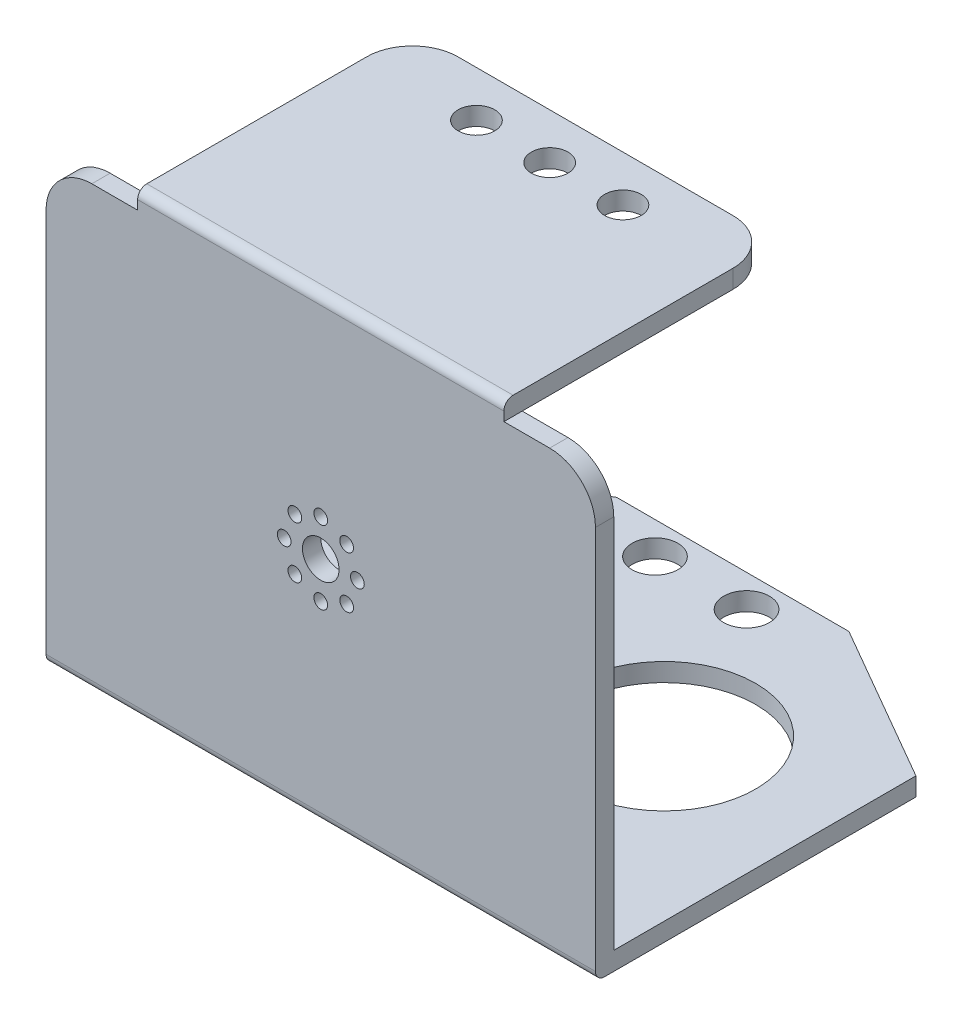
SolidWorks part; units mm, degrees
ref_plane "前视基准面" through (0, 0, 0) normal (0, 0, 1) x (1, 0, 0)
ref_plane "上视基准面" through (0, 0, 0) normal (0, 1, 0) x (1, 0, 0)
ref_plane "右视基准面" through (0, 0, 0) normal (1, 0, 0) x (0, 0, -1)
sketch "草图1" plane through (0, 0, 0) normal (0, 1, 0) x (1, 0, 0)
  line L0 (0, 0) -> (51111.788, 0) construction
  line L1 (0, 0) -> (0, 51111.788) construction
  line L2 (-12.6795, 0) -> (12.6795, 0)
  line L3 (12.6795, 0) -> (30, -10)
  line L4 (30, -10) -> (30, -45)
  line L5 (30, -45) -> (-30, -45)
  line L6 (-30, -45) -> (-30, -10)
  line L7 (-30, -10) -> (-12.6795, 0)
  dimension "D1" = 45
  dimension "D2" = 10
  dimension "D3" = 30
  dimension "D4" = 60
extrude "凸台-拉伸1" add sketch "草图1" along normal blind 2
sketch "草图2" plane through (0, 2, 0) normal (0, 1, 0) x (1, 0, 0)
  line L0 (30, -45) -> (30, -10) construction
  line L1 (-30, -45) -> (30, -45)
  line L2 (-30, -45) -> (-30, -43)
  line L3 (-30, -43) -> (30, -43)
  line L4 (30, -45) -> (30, -43)
  dimension "D1" = 2
extrude "凸台-拉伸2" add sketch "草图2" along normal blind 50 from surface starting at face at (0, 0, 18.3333)
fillet "圆角1" radius 1 1 edges at (0, 0, 45)
sketch "草图3" plane through (0, 0, 43) normal (0, 0, -1) x (-1, 0, 0)
  line L0 (0, 0) -> (0, 50000) construction
  line L1 (-20, 50) -> (20, 50)
  line L2 (-20, 50) -> (-20, 48)
  line L3 (-20, 48) -> (20, 48)
  line L4 (20, 50) -> (20, 48)
  line L5 (30, 50) -> (-30, 50) construction
  line L6 (30, 50) -> (30, 2) construction
  line L7 (-30, 50) -> (-20, 50)
  line L8 (-30, 50) -> (-30, 48)
  line L9 (-30, 48) -> (-20, 48)
  line L10 (-20, 50) -> (-20, 48)
  line L11 (20, 50) -> (30, 50)
  line L12 (20, 50) -> (20, 48)
  line L13 (20, 48) -> (30, 48)
  line L14 (30, 50) -> (30, 48)
  line M3 (30, 2) -> (30, 50)
  line M4 (30, 50) -> (-30, 50)
  line M5 (-30, 50) -> (-30, 2)
  dimension "D1" = 2
  dimension "D2" = 40
extrude "凸台-拉伸4" add sketch "草图3" along normal blind 30 from surface contours L3 L0 L1 L2 | L0 L3 L4 M4 region at (10, 49, 43) region at (-10, 49, 43) starting at face at (0, 25.5, 45)
extrude "切除-拉伸1" cut sketch "草图3<3>" against normal blind 30 contours L9 L2 M5 M4 | L4 L13 M3 M4 region at (25, 49, 43) region at (-25, 49, 43)
sketch "草图3<3>" plane through (0, 0, 43) normal (0, 0, -1) x (-1, 0, 0) same geometry as "草图3"
fillet "圆角4" radius 5 2 edges at (-30, 48, 44) (30, 48, 44)
fillet "圆角5" radius 1 1 edges at (0, 50, 45)
sketch "草图4" plane through (0, 50, 0) normal (0, 1, 0) x (1, 0, 0)
  line L0 (0, 0) -> (0, -50000) construction
  line L1 (-20, -15) -> (20, -15) construction
  circle A0 centre (0, -20) radius 2
  circle A1 centre (-8, -20) radius 2
  circle A2 centre (8, -20) radius 2
  dimension "D1" = 4
  dimension "D2" = 5
  dimension "D3" = 8
extrude "切除-拉伸2" cut sketch "草图4" against normal blind 30
fillet "圆角6" radius 5 2 edges at (20, 49, 15) (-20, 49, 15)
sketch "草图5" plane through (0, 0, 0) normal (0, -1, 0) x (1, 0, 0)
  line L1 (0, 0) -> (0, 50000) construction
  line L2 (12.6795, 0) -> (-12.6795, 0) construction
  line L3 (-30, 45) -> (30, 45) construction
  circle A9 centre (-12.5, 20) radius 2.5
  circle A15 centre (12.5, 20) radius 10
  point P10 (0, 0)
  point P11 (0, 0)
  dimension "D1" = 20
  dimension "D4" = 25
  dimension "D5" = 5
  dimension "D3" = 25
extrude "切除-拉伸4" cut sketch "草图5" against normal blind 30
sketch "草图6" plane through (0, 2, 0) normal (0, 1, 0) x (1, 0, 0)
  line L0 (0, 0) -> (0, -50000) construction
  line L1 (12.6795, 0) -> (-12.6795, 0) construction
  circle A0 centre (5, -3.5) radius 2.5
  circle A1 centre (-5, -3.5) radius 2.5
  dimension "D1" = 5
  dimension "D2" = 3.5
  dimension "D3" = 10
extrude "切除-拉伸5" cut sketch "草图6" against normal blind 10
sketch "草图7" plane through (0, 0, 45) normal (0, 0, 1) x (1, 0, 0)
  line L0 (0, 0) -> (0, 50000) construction
  line L1 (-20, 50) -> (20, 50) construction
  circle A0 centre (0, 25) radius 2
  circle A1 centre (0, 29) radius 0.75
  circle A2 centre (2.8284, 27.8284) radius 0.75
  circle A3 centre (4, 25) radius 0.75
  circle A4 centre (2.8284, 22.1716) radius 0.75
  circle A5 centre (0, 21) radius 0.75
  circle A6 centre (-2.8284, 22.1716) radius 0.75
  circle A7 centre (-4, 25) radius 0.75
  circle A8 centre (-2.8284, 27.8284) radius 0.75
  point P10 (-3.8857, 11.7832)
  point P11 (0, 0)
  point P25 (0, 25)
  dimension "D1" = 4
  dimension "D3" = 1.5
  dimension "D2" = 25
  dimension "D4" = 4
  dimension "D5" = 8
extrude "切除-拉伸6" cut sketch "草图7" against normal blind 10
